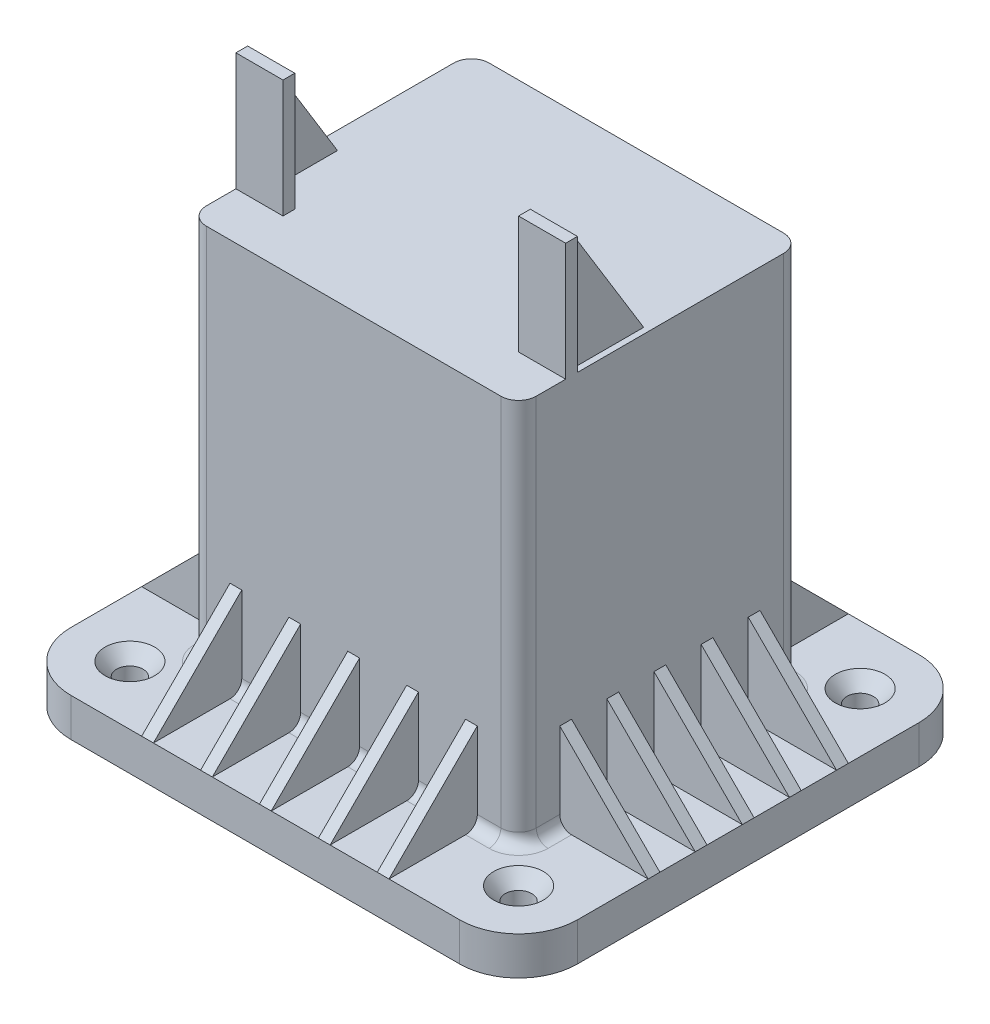
SolidWorks part; units mm, degrees
material "ABS"
ref_plane "Front Plane" through (0, 0, 0) normal (0, 0, 1) x (1, 0, 0)
ref_plane "Top Plane" through (0, 0, 0) normal (0, 1, 0) x (1, 0, 0)
ref_plane "Right Plane" through (0, 0, 0) normal (1, 0, 0) x (0, 0, -1)
sketch "Sketch1" plane through (0, 0, 0) normal (0, 0, 1) x (1, 0, 0)
  line L0 (0, 0) -> (0, 20)
  line L1 (0, 20) -> (-8, 20)
  line L2 (-8, 20) -> (-8, 0)
  line L3 (-8, 0) -> (0, 0)
  line L5 (48, 0) -> (-8, 0)
  line L6 (48, 0) -> (48, -8)
  line L7 (48, -8) -> (-8, -8)
  line L8 (-8, 0) -> (-8, -8)
  line L9 (40, 0) -> (48, 0)
  line L10 (40, 0) -> (40, 20)
  line L11 (40, 20) -> (48, 20)
  line L12 (48, 0) -> (48, 20)
  point P11 (40, 10)
  dimension "D1" = 40
  dimension "D2" = 20
  dimension "D3" = 8
  dimension "D4" = 8
extrude "Boss-Extrude1" add sketch "Sketch1" along normal blind 8 contours L3 L8 L7 L6 L5 region at (20, -4, 0)
extrude "Boss-Extrude2" add sketch "Sketch1<3>" against normal blind 40 contours L3 L8 L7 L6 L5 region at (20, -4, 0)
sketch "Sketch1<3>" plane through (0, 0, 0) normal (0, 0, 1) x (1, 0, 0) same geometry as "Sketch1"
extrude "Boss-Extrude3" add sketch "Sketch1<4>" against normal blind 2 contours L2 L3 L0 L1 | L5 L12 L11 L10 region at (-4, 10, 0) region at (44, 10, 0)
sketch "Sketch1<4>" plane through (0, 0, 0) normal (0, 0, 1) x (1, 0, 0) same geometry as "Sketch1"
ref_plane "Plane1" through (-7, 0, 0) normal (-1, 0, 0) x (0, 0, 1)
sketch "Sketch3" plane through (-7, 0, 0) normal (-1, 0, 0) x (0, 0, 1)
  line L0 (-2, 20) -> (-14.25, 0)
  line L1 (-2, 0) -> (-40, 0) construction
  dimension "D1" = 12.25
rib "Rib3" sketch "Sketch3" sketch "Sketch3" thickness 2 extrusion direction parallel to sketch draft on no parameters "D1"=2
ref_plane "Plane2" through (20, 0, 0) normal (-1, 0, 0) x (0, 0, 1)
mirror "Mirror2" about plane through (20, 0, 0) normal (-1, 0, 0) of "Rib3"
fillet "Fillet2" radius 3 4 edges at (48, -4, 8) (-8, -4, 8) (48, -4, -40) (-8, -4, -40)
sketch "Sketch4" plane through (0, -8, 0) normal (0, -1, 0) x (1, 0, 0)
  line L0 (48, 5) -> (48, -37) construction
  line L1 (-5, -40) -> (45, -40)
  line L2 (-8, -37) -> (-8, 5)
  line L3 (-5, 8) -> (45, 8)
  line L4 (48, -37) -> (48, 5)
  line L5 (45, 8) -> (-5, 8) construction
  line L6 (-8, 5) -> (-8, -37) construction
  line L7 (45, -40) -> (-5, -40) construction
  arc A0 (-8, 5) -> (-5, 8) centre (-5, 5) cw
  arc A1 (45, 8) -> (48, 5) centre (45, 5) cw
  arc A2 (48, -37) -> (45, -40) centre (45, -37) cw
  arc A3 (-5, -40) -> (-8, -37) centre (-5, -37) cw
  dimension "D1" = 3
extrude "Boss-Extrude4" add sketch "Sketch4" along normal blind 64
sketch "Sketch5" plane through (0, -72, 0) normal (0, -1, 0) x (1, 0, 0)
  line L0 (45, 8) -> (-5, 8) construction
  line L1 (-23, -55) -> (63, -55)
  line L2 (-23, -55) -> (-23, 23)
  line L3 (-23, 23) -> (63, 23)
  line L4 (63, -55) -> (63, 23)
  line L5 (-5, -40) -> (45, -40) construction
  line L6 (48, -37) -> (48, 5) construction
  line L7 (-8, 5) -> (-8, -37) construction
  dimension "D1" = 15
  dimension "D2" = 15
  dimension "D3" = 15
  dimension "D4" = 15
extrude "Boss-Extrude5" add sketch "Sketch5" against normal blind 6.5
fillet "Fillet3" radius 10 4 edges at (-23, -68.75, 23) (63, -68.75, 23) (63, -68.75, -55) (-23, -68.75, -55)
hole_wizard "CSK for #8 Flat Head Machine Screw1" positions "3DSketch1" profile "Sketch6" countersink size "#8" standard "ANSI Inch" end condition up to next
sketch3d "3DSketch1"
  arc A2 (-13, -65.5, -55) -> (-23, -65.5, -45) centre (-13, -65.5, -45) ccw construction
  arc A3 (-23, -65.5, 13) -> (-13, -65.5, 23) centre (-13, -65.5, 13) ccw construction
  arc A4 (63, -65.5, -45) -> (53, -65.5, -55) centre (53, -65.5, -45) ccw construction
  arc A5 (53, -65.5, 23) -> (63, -65.5, 13) centre (53, -65.5, 13) ccw construction
  point P0 (-13, -65.5, 13)
  point P2 (-13, -65.5, -45)
  point P4 (53, -65.5, 13)
  point P6 (53, -65.5, -45)
  point P9 (0, 0, 0)
  point P18 (0, 0, 0)
  point P22 (-13, -55.5, -45)
  point P23 (0, 0, 0)
  point P27 (-13, -55.5, 13)
  point P28 (0, 0, 0)
  point P32 (53, -55.5, -45)
  point P33 (0, 0, 0)
  point P37 (53, -55.5, 13)
sketch "Sketch6" plane through (-13, -65.5, 13) normal (1, 0, 0) x (0, 0, 1)
  line L0 (0, 0) -> (0, 6.5)
  line L1 (0, 6.5) -> (2.2479, 6.5)
  line L2 (2.2479, 6.5) -> (2.2479, 2.2645)
  line L3 (2.2479, 2.2645) -> (4.2164, 0)
  line L5 (4.2164, 0) -> (0, 0)
  line L6 (-2.2479, 2.2645) -> (-4.2164, 0) construction
  line L11 (0, -6.35) -> (0, 107.95) construction
  dimension "Thru Hole Dia." = 4.4958
  dimension "Thru Hole Depth" = 6.5
  dimension "Near C'Sink Dia." = 8.4328
  dimension "Near C'Sink Angle" = 82
fillet "Fillet4" radius 2 8 edges at (47.1213, -65.5, -39.1213) (48, -65.5, -16) (47.1213, -65.5, 7.1213) (20, -65.5, 8) (-7.1213, -65.5, 7.1213) (-8, -65.5, -16) (-7.1213, -65.5, -39.1213) (20, -65.5, -40)
ref_plane "Plane3" through (20, 0, 0) normal (-1, 0, 0) x (0, 0, 1)
sketch "Sketch7" plane through (20, 0, 0) normal (-1, 0, 0) x (0, 0, 1)
  line L0 (-55, -65.5) -> (-40, -50.5)
  line L1 (-40, -63.5) -> (-40, 0) construction
  line L2 (-45, -65.5) -> (-55, -65.5) construction
  dimension "D1" = 15
rib "Rib4" sketch "Sketch7" sketch "Sketch7" thickness 2 extrusion direction parallel to sketch draft on no parameters "D1"=2
pattern_linear "LPattern1" count 3 spacing 10 along (-1, 0, 0) count 3 spacing 10 along (1, 0, 0) of "Rib4" pattern seed only yes
ref_plane "Plane4" through (0, 0, -16) normal (0, 0, -1) x (-1, 0, 0)
mirror "Mirror3" about plane through (0, 0, -16) normal (0, 0, -1) of "LPattern1"
sketch "Sketch8" plane through (0, 0, -16) normal (0, 0, -1) x (-1, 0, 0)
  line L0 (8, -50.5) -> (23, -65.5)
  line L1 (8, 0) -> (8, -63.5) construction
  line L2 (23, -65.5) -> (13, -65.5) construction
  line L3 (13, -65.5) -> (1, -65.5) construction
  dimension "D1" = 15
rib "Rib5" sketch "Sketch8" sketch "Sketch8" thickness 2 extrusion direction parallel to sketch draft on no parameters "D1"=2
pattern_linear "LPattern2" count 3 spacing 8 along (0, 0, -1) count 3 spacing 8 along (0, 0, 1) of "Rib5" pattern seed only yes
mirror "Mirror4" about plane through (20, 0, 0) normal (-1, 0, 0) of "LPattern2"
